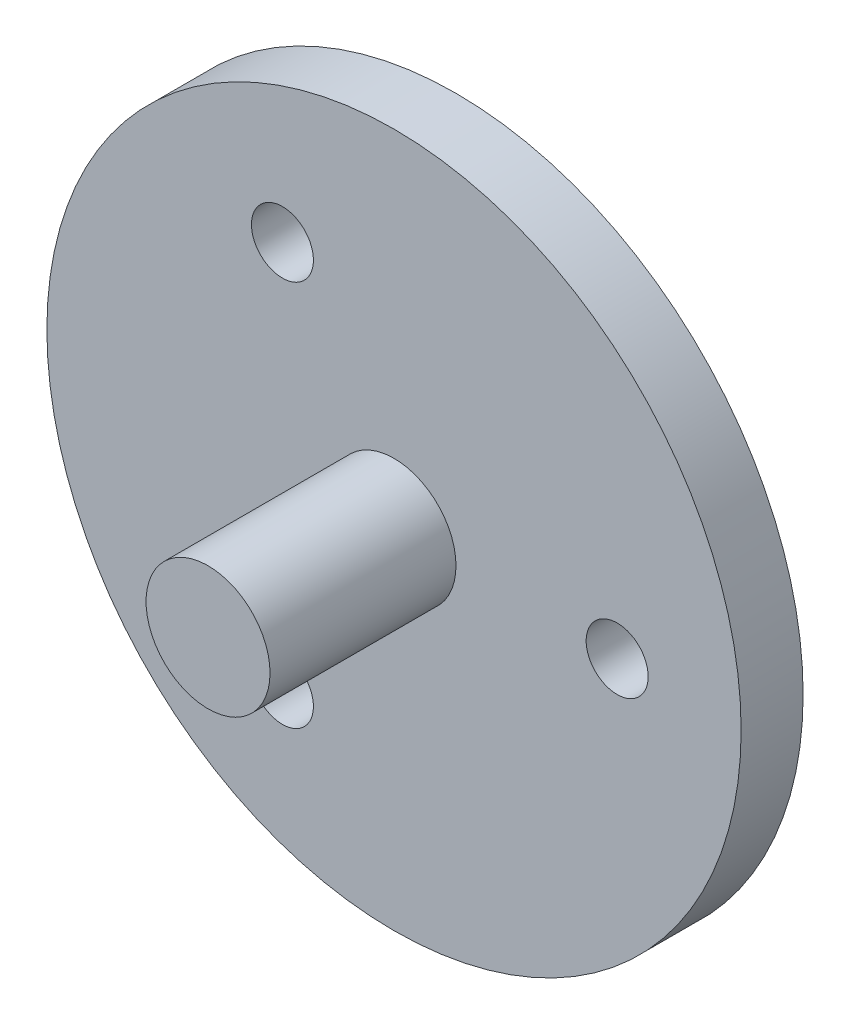
SolidWorks part; units mm, degrees
ref_plane "前视基准面" through (0, 0, 0) normal (0, 0, 1) x (1, 0, 0)
ref_plane "上视基准面" through (0, 0, 0) normal (0, 1, 0) x (1, 0, 0)
ref_plane "右视基准面" through (0, 0, 0) normal (1, 0, 0) x (0, 0, -1)
other "Configuration Table"
sketch "Sketch1" plane through (0, 0, 0) normal (0, 0, 1) x (1, 0, 0)
  circle A0 centre (0, 0) radius 56
extrude "Boss-Extrude1" add sketch "Sketch1" along normal blind 10
ref_plane "Plane1" through (0, 0, 10) normal (0, 0, 1) x (1, 0, 0)
sketch "Sketch2" plane through (0, 0, 10) normal (0, 0, 1) x (1, 0, 0)
  circle A0 centre (0, 0) radius 10
extrude "Boss-Extrude2" add sketch "Sketch2" along normal blind 30
sketch "Sketch3" plane through (0, 0, 10) normal (0, 0, 1) x (1, 0, 0)
  circle A0 centre (36, 0) radius 5
  circle A1 centre (-18, 31.1769) radius 5
  circle A2 centre (-18, -31.1769) radius 5
extrude "Cut-Extrude1" cut sketch "Sketch3" against normal blind 10
sketch3d "3DSketch1"
  line L0 (0, 0, 0) -> (0, 0, 50) construction
ref_axis "output_axis" through (0, 0, 0) along (0, 0, 1)
sketch3d "3DSketch2"
  line L0 (36, 0, 0) -> (36, 0, 10) construction
ref_axis "pin_axis_1" through (36, 0, 0) along (0, 0, 1)
sketch3d "3DSketch3"
  line L0 (-18, 31.1769, 0) -> (-18, 31.1769, 10) construction
ref_axis "pin_axis_2" through (-18, 31.1769, 0) along (0, 0, 1)
sketch3d "3DSketch4"
  line L0 (-18, -31.1769, 0) -> (-18, -31.1769, 10) construction
ref_axis "pin_axis_3" through (-18, -31.1769, 0) along (0, 0, 1)
ref_plane "mounting_face" through (0, 0, 10) normal (0, 0, 1) x (1, 0, 0)
